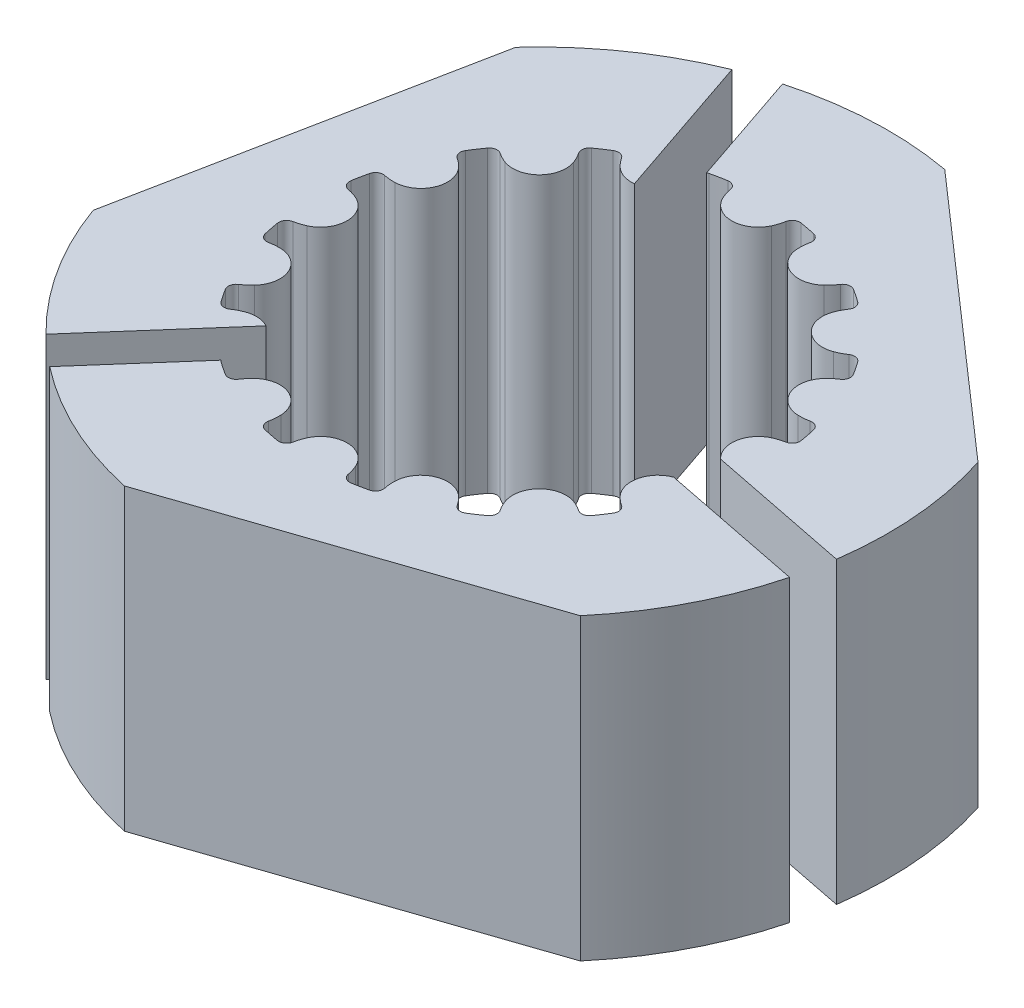
SolidWorks part; units mm, degrees
material "Alum Plate"
ref_plane "Front Plane" through (0, 0, 0) normal (0, 0, 1) x (1, 0, 0)
ref_plane "Top Plane" through (0, 0, 0) normal (0, 1, 0) x (1, 0, 0)
ref_plane "Right Plane" through (0, 0, 0) normal (1, 0, 0) x (0, 0, -1)
other "Bounding Box"
ref_plane "Default Plane" through (-8.9266, -12.7485, 0) normal (-0.1736, 0.9848, 0) x (0.9848, 0.1736, 0)
sketch "Sketch1" plane through (0, 0, 0) normal (0, 1, 0) x (1, 0, 0)
  line L0 (0, -7.8245) -> (0, 0) construction
  circle A0 centre (0, 0) radius 2.5
  arc B0 (-1.8508, -6.777) -> (-1.6633, -7.0715) centre (-1.6061, -6.8282) ccw
  arc B1 (-1.6633, -7.0715) -> (-1.1695, -7.1697) centre (0, 0) ccw
  arc B2 (-1.1695, -7.1697) -> (-0.8836, -6.9694) centre (-1.1292, -6.923) ccw
  arc B3 (-0.7739, -6.6229) -> (-0.8836, -6.9694) centre (0.61, -7.2516) ccw
  arc B4 (0.7739, -6.6229) -> (-0.7739, -6.6229) centre (0, -6.9745) ccw
  arc B5 (0.8836, -6.9694) -> (0.7739, -6.6229) centre (-0.61, -7.2516) ccw
  arc B6 (0.8836, -6.9694) -> (1.1695, -7.1697) centre (1.1292, -6.923) ccw
  arc B7 (1.1695, -7.1697) -> (1.6633, -7.0715) centre (0, 0) ccw
  arc B8 (1.6633, -7.0715) -> (1.8508, -6.777) centre (1.6061, -6.8282) ccw
  arc B9 (1.8195, -6.4149) -> (1.8508, -6.777) centre (3.3386, -6.4662) ccw
  arc B10 (3.2495, -5.8226) -> (1.8195, -6.4149) centre (2.669, -6.4436) ccw
  arc B11 (3.4834, -6.1008) -> (3.2495, -5.8226) centre (2.2115, -6.9331) ccw
  arc B12 (3.4834, -6.1008) -> (3.8242, -6.1764) centre (3.6926, -5.9639) ccw
  arc B13 (3.8242, -6.1764) -> (4.2428, -5.8967) centre (0, 0) ccw
  arc B14 (4.2428, -5.8967) -> (4.3033, -5.5529) centre (4.0968, -5.6938) ccw
  arc B15 (4.1359, -5.2303) -> (4.3033, -5.5529) centre (5.559, -4.6963) ccw
  arc B16 (5.2303, -4.1359) -> (4.1359, -5.2303) centre (4.9317, -4.9317) ccw
  arc B17 (5.5529, -4.3033) -> (5.2303, -4.1359) centre (4.6963, -5.559) ccw
  arc B18 (5.5529, -4.3033) -> (5.8967, -4.2428) centre (5.6938, -4.0968) ccw
  arc B19 (5.8967, -4.2428) -> (6.1764, -3.8242) centre (0, 0) ccw
  arc B20 (6.1764, -3.8242) -> (6.1008, -3.4834) centre (5.9639, -3.6926) ccw
  arc B21 (5.8226, -3.2495) -> (6.1008, -3.4834) centre (6.9331, -2.2115) ccw
  arc B22 (6.4149, -1.8195) -> (5.8226, -3.2495) centre (6.4436, -2.669) ccw
  arc B23 (6.777, -1.8508) -> (6.4149, -1.8195) centre (6.4662, -3.3386) ccw
  arc B24 (6.777, -1.8508) -> (7.0715, -1.6633) centre (6.8282, -1.6061) ccw
  arc B25 (7.0715, -1.6633) -> (7.1697, -1.1695) centre (0, 0) ccw
  arc B26 (7.1697, -1.1695) -> (6.9694, -0.8836) centre (6.923, -1.1292) ccw
  arc B27 (6.6229, -0.7739) -> (6.9694, -0.8836) centre (7.2516, 0.61) ccw
  arc B28 (6.6229, 0.7739) -> (6.6229, -0.7739) centre (6.9745, 0) ccw
  arc B29 (6.9694, 0.8836) -> (6.6229, 0.7739) centre (7.2516, -0.61) ccw
  arc B30 (6.9694, 0.8836) -> (7.1697, 1.1695) centre (6.923, 1.1292) ccw
  arc B31 (7.1697, 1.1695) -> (7.0715, 1.6633) centre (0, 0) ccw
  arc B32 (7.0715, 1.6633) -> (6.777, 1.8508) centre (6.8282, 1.6061) ccw
  arc B33 (6.4149, 1.8195) -> (6.777, 1.8508) centre (6.4662, 3.3386) ccw
  arc B34 (5.8226, 3.2495) -> (6.4149, 1.8195) centre (6.4436, 2.669) ccw
  arc B35 (6.1008, 3.4834) -> (5.8226, 3.2495) centre (6.9331, 2.2115) ccw
  arc B36 (6.1008, 3.4834) -> (6.1764, 3.8242) centre (5.9639, 3.6926) ccw
  arc B37 (6.1764, 3.8242) -> (5.8967, 4.2428) centre (0, 0) ccw
  arc B38 (5.8967, 4.2428) -> (5.5529, 4.3033) centre (5.6938, 4.0968) ccw
  arc B39 (5.2303, 4.1359) -> (5.5529, 4.3033) centre (4.6963, 5.559) ccw
  arc B40 (4.1359, 5.2303) -> (5.2303, 4.1359) centre (4.9317, 4.9317) ccw
  arc B41 (4.3033, 5.5529) -> (4.1359, 5.2303) centre (5.559, 4.6963) ccw
  arc B42 (4.3033, 5.5529) -> (4.2428, 5.8967) centre (4.0968, 5.6938) ccw
  arc B43 (4.2428, 5.8967) -> (3.8242, 6.1764) centre (0, 0) ccw
  arc B44 (3.8242, 6.1764) -> (3.4834, 6.1008) centre (3.6926, 5.9639) ccw
  arc B45 (3.2495, 5.8226) -> (3.4834, 6.1008) centre (2.2115, 6.9331) ccw
  arc B46 (1.8195, 6.4149) -> (3.2495, 5.8226) centre (2.669, 6.4436) ccw
  arc B47 (1.8508, 6.777) -> (1.8195, 6.4149) centre (3.3386, 6.4662) ccw
  arc B48 (1.8508, 6.777) -> (1.6633, 7.0715) centre (1.6061, 6.8282) ccw
  arc B49 (1.6633, 7.0715) -> (1.1695, 7.1697) centre (0, 0) ccw
  arc B50 (1.1695, 7.1697) -> (0.8836, 6.9694) centre (1.1292, 6.923) ccw
  arc B51 (0.7739, 6.6229) -> (0.8836, 6.9694) centre (-0.61, 7.2516) ccw
  arc B52 (-0.7739, 6.6229) -> (0.7739, 6.6229) centre (0, 6.9745) ccw
  arc B53 (-0.8836, 6.9694) -> (-0.7739, 6.6229) centre (0.61, 7.2516) ccw
  arc B54 (-0.8836, 6.9694) -> (-1.1695, 7.1697) centre (-1.1292, 6.923) ccw
  arc B55 (-1.1695, 7.1697) -> (-1.6633, 7.0715) centre (0, 0) ccw
  arc B56 (-1.6633, 7.0715) -> (-1.8508, 6.777) centre (-1.6061, 6.8282) ccw
  arc B57 (-1.8195, 6.4149) -> (-1.8508, 6.777) centre (-3.3386, 6.4662) ccw
  arc B58 (-3.2495, 5.8226) -> (-1.8195, 6.4149) centre (-2.669, 6.4436) ccw
  arc B59 (-3.4834, 6.1008) -> (-3.2495, 5.8226) centre (-2.2115, 6.9331) ccw
  arc B60 (-3.4834, 6.1008) -> (-3.8242, 6.1764) centre (-3.6926, 5.9639) ccw
  arc B61 (-3.8242, 6.1764) -> (-4.2428, 5.8967) centre (0, 0) ccw
  arc B62 (-4.2428, 5.8967) -> (-4.3033, 5.5529) centre (-4.0968, 5.6938) ccw
  arc B63 (-4.1359, 5.2303) -> (-4.3033, 5.5529) centre (-5.559, 4.6963) ccw
  arc B64 (-5.2303, 4.1359) -> (-4.1359, 5.2303) centre (-4.9317, 4.9317) ccw
  arc B65 (-5.5529, 4.3033) -> (-5.2303, 4.1359) centre (-4.6963, 5.559) ccw
  arc B66 (-5.5529, 4.3033) -> (-5.8967, 4.2428) centre (-5.6938, 4.0968) ccw
  arc B67 (-5.8967, 4.2428) -> (-6.1764, 3.8242) centre (0, 0) ccw
  arc B68 (-6.1764, 3.8242) -> (-6.1008, 3.4834) centre (-5.9639, 3.6926) ccw
  arc B69 (-5.8226, 3.2495) -> (-6.1008, 3.4834) centre (-6.9331, 2.2115) ccw
  arc B70 (-6.4149, 1.8195) -> (-5.8226, 3.2495) centre (-6.4436, 2.669) ccw
  arc B71 (-6.777, 1.8508) -> (-6.4149, 1.8195) centre (-6.4662, 3.3386) ccw
  arc B72 (-6.777, 1.8508) -> (-7.0715, 1.6633) centre (-6.8282, 1.6061) ccw
  arc B73 (-7.0715, 1.6633) -> (-7.1697, 1.1695) centre (0, 0) ccw
  arc B74 (-7.1697, 1.1695) -> (-6.9694, 0.8836) centre (-6.923, 1.1292) ccw
  arc B75 (-6.6229, 0.7739) -> (-6.9694, 0.8836) centre (-7.2516, -0.61) ccw
  arc B76 (-6.6229, -0.7739) -> (-6.6229, 0.7739) centre (-6.9745, 0) ccw
  arc B77 (-6.9694, -0.8836) -> (-6.6229, -0.7739) centre (-7.2516, 0.61) ccw
  arc B78 (-6.9694, -0.8836) -> (-7.1697, -1.1695) centre (-6.923, -1.1292) ccw
  arc B79 (-7.1697, -1.1695) -> (-7.0715, -1.6633) centre (0, 0) ccw
  arc B80 (-7.0715, -1.6633) -> (-6.777, -1.8508) centre (-6.8282, -1.6061) ccw
  arc B81 (-6.4149, -1.8195) -> (-6.777, -1.8508) centre (-6.4662, -3.3386) ccw
  arc B82 (-5.8226, -3.2495) -> (-6.4149, -1.8195) centre (-6.4436, -2.669) ccw
  arc B83 (-6.1008, -3.4834) -> (-5.8226, -3.2495) centre (-6.9331, -2.2115) ccw
  arc B84 (-6.1008, -3.4834) -> (-6.1764, -3.8242) centre (-5.9639, -3.6926) ccw
  arc B85 (-6.1764, -3.8242) -> (-5.8967, -4.2428) centre (0, 0) ccw
  arc B86 (-5.8967, -4.2428) -> (-5.5529, -4.3033) centre (-5.6938, -4.0968) ccw
  arc B87 (-5.2303, -4.1359) -> (-5.5529, -4.3033) centre (-4.6963, -5.559) ccw
  arc B88 (-4.1359, -5.2303) -> (-5.2303, -4.1359) centre (-4.9317, -4.9317) ccw
  arc B89 (-4.3033, -5.5529) -> (-4.1359, -5.2303) centre (-5.559, -4.6963) ccw
  arc B90 (-4.3033, -5.5529) -> (-4.2428, -5.8967) centre (-4.0968, -5.6938) ccw
  arc B91 (-4.2428, -5.8967) -> (-3.8242, -6.1764) centre (0, 0) ccw
  arc B92 (-3.8242, -6.1764) -> (-3.4834, -6.1008) centre (-3.6926, -5.9639) ccw
  arc B93 (-3.2495, -5.8226) -> (-3.4834, -6.1008) centre (-2.2115, -6.9331) ccw
  arc B94 (-1.8195, -6.4149) -> (-3.2495, -5.8226) centre (-2.669, -6.4436) ccw
  arc B95 (-1.8508, -6.777) -> (-1.8195, -6.4149) centre (-3.3386, -6.4662) ccw
  dimension "D1" = 5
sketch_block_instance "Block-GT2 16 Tooth Profile-1"
sketch_block "Block-GT2 16 Tooth Profile"
extrude "Boss-Extrude1" add sketch "Sketch1" along normal mid plane 9.525
sketch "Sketch2" plane through (0, -4.7625, 0) normal (0, -1, 0) x (1, 0, 0)
  circle A0 centre (0, 0) radius 7.9375
  circle A1 centre (0, 0) radius 2.5 construction
  circle A2 centre (0, 0) radius 2.5
  dimension "D1" = 15.875
extrude "Boss-Extrude2" add sketch "Sketch2" along normal blind 0.762 separate body
sketch "Sketch4" plane through (0, -4.7625, 0) normal (0, -1, 0) x (1, 0, 0)
  line L0 (-4.3596, 0.8672) -> (0, 0) construction
  line L1 (0, 0) -> (4.3596, -0.8672) construction
  line L2 (-7.1249, 1.4172) -> (-4.3596, 0.8672) construction
  circle A0 centre (-4.3596, 0.8672) radius 1
  circle A1 centre (4.3596, -0.8672) radius 1
  arc A2 (-7.0715, 1.6633) -> (-7.1697, 1.1695) centre (0, 0) ccw construction
  dimension "D1" = 2
  dimension "D2" = 4.445
extrude "Cut-Extrude2" cut sketch "Sketch4" against normal through all
sketch "Sketch5" plane through (0, -4.7625, 0) normal (0, 1, 0) x (1, 0, 0)
  circle A0 centre (-4.3596, -0.8672) radius 1.25
  circle A1 centre (4.3596, 0.8672) radius 1.25
  dimension "D1" = 2.5
extrude "Cut-Extrude3" cut sketch "Sketch5" against normal through all
delete or keep bodies "Body-Delete/Keep 1" [suppressed] type delete bodies bodies 111
delete or keep bodies "Body-Delete/Keep 2" [suppressed] type delete bodies bodies 108
sketch "Sketch6" plane through (0, 4.7625, 0) normal (0, 1, 0) x (1, 0, 0)
  line L2 (0, 0) -> (-3.572, 10.5228) construction
  line L3 (-7.327, -8.3548) -> (0, 0) construction
  line L4 (0, 0) -> (10.899, -2.1679) construction
  line L5 (-3.572, 10.5228) -> (10.899, -2.1679) construction
  line L6 (10.899, -2.1679) -> (-7.327, -8.3548) construction
  line L7 (-7.327, -8.3548) -> (-3.572, 10.5228) construction
  line L8 (-3.572, 10.5228) -> (-10.899, 2.1679) construction
  line L9 (-10.899, 2.1679) -> (-7.327, -8.3548) construction
  line L10 (-7.327, -8.3548) -> (3.572, -10.5228) construction
  line L11 (3.572, -10.5228) -> (10.899, -2.1679) construction
  line L12 (10.899, -2.1679) -> (7.327, 8.3548) construction
  line L13 (7.327, 8.3548) -> (-3.572, 10.5228) construction
  line L14 (0.6013, 0.2041) -> (-2.9707, 10.7269)
  line L15 (-6.8496, -8.7735) -> (0.4774, -0.4187)
  line L16 (-0.1239, -0.6228) -> (10.7751, -2.7907)
  line L17 (-0.6013, -0.2041) -> (-4.1733, 10.3186)
  line L18 (-7.8044, -7.9361) -> (-0.4774, 0.4187)
  line L19 (0.1239, 0.6228) -> (11.0229, -1.5451)
  line L20 (-8.2253, 7.4721) -> (-10.4586, -3.7556)
  line L21 (-2.3583, -10.8594) -> (8.4818, -7.1797)
  line L22 (1.9769, 10.9352) -> (10.5837, 3.3873)
  line L23 (7.327, 8.3548) -> (6.2803, 7.1613) construction
  line L24 (3.0617, -9.0195) -> (3.572, -10.5228) construction
  line L25 (-10.899, 2.1679) -> (-9.342, 1.8582) construction
  circle A1 centre (0, 0) radius 11.1125
  arc A96 (-1.8508, -6.777) -> (-1.8195, -6.4149) centre (-3.3386, -6.4662) ccw
  arc A97 (-1.8508, -6.777) -> (-1.6633, -7.0715) centre (-1.6061, -6.8282) ccw
  arc A98 (-1.6633, -7.0715) -> (-1.1695, -7.1697) centre (0, 0) ccw
  arc A99 (-1.1695, -7.1697) -> (-0.8836, -6.9694) centre (-1.1292, -6.923) ccw
  arc A100 (-0.7739, -6.6229) -> (-0.8836, -6.9694) centre (0.61, -7.2516) ccw
  arc A101 (0.7739, -6.6229) -> (-0.7739, -6.6229) centre (0, -6.9745) ccw
  arc A102 (0.8836, -6.9694) -> (0.7739, -6.6229) centre (-0.61, -7.2516) ccw
  arc A103 (0.8836, -6.9694) -> (1.1695, -7.1697) centre (1.1292, -6.923) ccw
  arc A104 (1.1695, -7.1697) -> (1.6633, -7.0715) centre (0, 0) ccw
  arc A105 (1.6633, -7.0715) -> (1.8508, -6.777) centre (1.6061, -6.8282) ccw
  arc A106 (1.8195, -6.4149) -> (1.8508, -6.777) centre (3.3386, -6.4662) ccw
  arc A107 (3.2495, -5.8226) -> (1.8195, -6.4149) centre (2.669, -6.4436) ccw
  arc A108 (3.4834, -6.1008) -> (3.2495, -5.8226) centre (2.2115, -6.9331) ccw
  arc A109 (3.4834, -6.1008) -> (3.8242, -6.1764) centre (3.6926, -5.9639) ccw
  arc A110 (3.8242, -6.1764) -> (4.2428, -5.8967) centre (0, 0) ccw
  arc A111 (4.2428, -5.8967) -> (4.3033, -5.5529) centre (4.0968, -5.6938) ccw
  arc A112 (4.1359, -5.2303) -> (4.3033, -5.5529) centre (5.559, -4.6963) ccw
  arc A113 (5.2303, -4.1359) -> (4.1359, -5.2303) centre (4.9317, -4.9317) ccw
  arc A114 (5.5529, -4.3033) -> (5.2303, -4.1359) centre (4.6963, -5.559) ccw
  arc A115 (5.5529, -4.3033) -> (5.8967, -4.2428) centre (5.6938, -4.0968) ccw
  arc A116 (5.8967, -4.2428) -> (6.1764, -3.8242) centre (0, 0) ccw
  arc A117 (6.1764, -3.8242) -> (6.1008, -3.4834) centre (5.9639, -3.6926) ccw
  arc A118 (5.8226, -3.2495) -> (6.1008, -3.4834) centre (6.9331, -2.2115) ccw
  arc A119 (6.4149, -1.8195) -> (5.8226, -3.2495) centre (6.4436, -2.669) ccw
  arc A120 (6.777, -1.8508) -> (6.4149, -1.8195) centre (6.4662, -3.3386) ccw
  arc A121 (6.777, -1.8508) -> (7.0715, -1.6633) centre (6.8282, -1.6061) ccw
  arc A122 (7.0715, -1.6633) -> (7.1697, -1.1695) centre (0, 0) ccw
  arc A123 (7.1697, -1.1695) -> (6.9694, -0.8836) centre (6.923, -1.1292) ccw
  arc A124 (6.6229, -0.7739) -> (6.9694, -0.8836) centre (7.2516, 0.61) ccw
  arc A125 (6.6229, 0.7739) -> (6.6229, -0.7739) centre (6.9745, 0) ccw
  arc A126 (6.9694, 0.8836) -> (6.6229, 0.7739) centre (7.2516, -0.61) ccw
  arc A127 (6.9694, 0.8836) -> (7.1697, 1.1695) centre (6.923, 1.1292) ccw
  arc A128 (7.1697, 1.1695) -> (7.0715, 1.6633) centre (0, 0) ccw
  arc A129 (7.0715, 1.6633) -> (6.777, 1.8508) centre (6.8282, 1.6061) ccw
  arc A130 (6.4149, 1.8195) -> (6.777, 1.8508) centre (6.4662, 3.3386) ccw
  arc A131 (5.8226, 3.2495) -> (6.4149, 1.8195) centre (6.4436, 2.669) ccw
  arc A132 (6.1008, 3.4834) -> (5.8226, 3.2495) centre (6.9331, 2.2115) ccw
  arc A133 (6.1008, 3.4834) -> (6.1764, 3.8242) centre (5.9639, 3.6926) ccw
  arc A134 (6.1764, 3.8242) -> (5.8967, 4.2428) centre (0, 0) ccw
  arc A135 (5.8967, 4.2428) -> (5.5529, 4.3033) centre (5.6938, 4.0968) ccw
  arc A136 (5.2303, 4.1359) -> (5.5529, 4.3033) centre (4.6963, 5.559) ccw
  arc A137 (4.1359, 5.2303) -> (5.2303, 4.1359) centre (4.9317, 4.9317) ccw
  arc A138 (4.3033, 5.5529) -> (4.1359, 5.2303) centre (5.559, 4.6963) ccw
  arc A139 (4.3033, 5.5529) -> (4.2428, 5.8967) centre (4.0968, 5.6938) ccw
  arc A140 (4.2428, 5.8967) -> (3.8242, 6.1764) centre (0, 0) ccw
  arc A141 (3.8242, 6.1764) -> (3.4834, 6.1008) centre (3.6926, 5.9639) ccw
  arc A142 (3.2495, 5.8226) -> (3.4834, 6.1008) centre (2.2115, 6.9331) ccw
  arc A143 (1.8195, 6.4149) -> (3.2495, 5.8226) centre (2.669, 6.4436) ccw
  arc A144 (1.8508, 6.777) -> (1.8195, 6.4149) centre (3.3386, 6.4662) ccw
  arc A145 (1.8508, 6.777) -> (1.6633, 7.0715) centre (1.6061, 6.8282) ccw
  arc A146 (1.6633, 7.0715) -> (1.1695, 7.1697) centre (0, 0) ccw
  arc A147 (1.1695, 7.1697) -> (0.8836, 6.9694) centre (1.1292, 6.923) ccw
  arc A148 (0.7739, 6.6229) -> (0.8836, 6.9694) centre (-0.61, 7.2516) ccw
  arc A149 (-0.7739, 6.6229) -> (0.7739, 6.6229) centre (0, 6.9745) ccw
  arc A150 (-0.8836, 6.9694) -> (-0.7739, 6.6229) centre (0.61, 7.2516) ccw
  arc A151 (-0.8836, 6.9694) -> (-1.1695, 7.1697) centre (-1.1292, 6.923) ccw
  arc A152 (-1.1695, 7.1697) -> (-1.6633, 7.0715) centre (0, 0) ccw
  arc A153 (-1.6633, 7.0715) -> (-1.8508, 6.777) centre (-1.6061, 6.8282) ccw
  arc A154 (-1.8195, 6.4149) -> (-1.8508, 6.777) centre (-3.3386, 6.4662) ccw
  arc A155 (-3.2495, 5.8226) -> (-1.8195, 6.4149) centre (-2.669, 6.4436) ccw
  arc A156 (-3.4834, 6.1008) -> (-3.2495, 5.8226) centre (-2.2115, 6.9331) ccw
  arc A157 (-3.4834, 6.1008) -> (-3.8242, 6.1764) centre (-3.6926, 5.9639) ccw
  arc A158 (-3.8242, 6.1764) -> (-4.2428, 5.8967) centre (0, 0) ccw
  arc A159 (-4.2428, 5.8967) -> (-4.3033, 5.5529) centre (-4.0968, 5.6938) ccw
  arc A160 (-4.1359, 5.2303) -> (-4.3033, 5.5529) centre (-5.559, 4.6963) ccw
  arc A161 (-5.2303, 4.1359) -> (-4.1359, 5.2303) centre (-4.9317, 4.9317) ccw
  arc A162 (-5.5529, 4.3033) -> (-5.2303, 4.1359) centre (-4.6963, 5.559) ccw
  arc A163 (-5.5529, 4.3033) -> (-5.8967, 4.2428) centre (-5.6938, 4.0968) ccw
  arc A164 (-5.8967, 4.2428) -> (-6.1764, 3.8242) centre (0, 0) ccw
  arc A165 (-6.1764, 3.8242) -> (-6.1008, 3.4834) centre (-5.9639, 3.6926) ccw
  arc A166 (-5.8226, 3.2495) -> (-6.1008, 3.4834) centre (-6.9331, 2.2115) ccw
  arc A167 (-6.4149, 1.8195) -> (-5.8226, 3.2495) centre (-6.4436, 2.669) ccw
  arc A168 (-6.777, 1.8508) -> (-6.4149, 1.8195) centre (-6.4662, 3.3386) ccw
  arc A169 (-6.777, 1.8508) -> (-7.0715, 1.6633) centre (-6.8282, 1.6061) ccw
  arc A170 (-7.0715, 1.6633) -> (-7.1697, 1.1695) centre (0, 0) ccw
  arc A171 (-7.1697, 1.1695) -> (-6.9694, 0.8836) centre (-6.923, 1.1292) ccw
  arc A172 (-6.6229, 0.7739) -> (-6.9694, 0.8836) centre (-7.2516, -0.61) ccw
  arc A173 (-6.6229, -0.7739) -> (-6.6229, 0.7739) centre (-6.9745, 0) ccw
  arc A174 (-6.9694, -0.8836) -> (-6.6229, -0.7739) centre (-7.2516, 0.61) ccw
  arc A175 (-6.9694, -0.8836) -> (-7.1697, -1.1695) centre (-6.923, -1.1292) ccw
  arc A176 (-7.1697, -1.1695) -> (-7.0715, -1.6633) centre (0, 0) ccw
  arc A177 (-7.0715, -1.6633) -> (-6.777, -1.8508) centre (-6.8282, -1.6061) ccw
  arc A178 (-6.4149, -1.8195) -> (-6.777, -1.8508) centre (-6.4662, -3.3386) ccw
  arc A179 (-5.8226, -3.2495) -> (-6.4149, -1.8195) centre (-6.4436, -2.669) ccw
  arc A180 (-6.1008, -3.4834) -> (-5.8226, -3.2495) centre (-6.9331, -2.2115) ccw
  arc A181 (-6.1008, -3.4834) -> (-6.1764, -3.8242) centre (-5.9639, -3.6926) ccw
  arc A182 (-6.1764, -3.8242) -> (-5.8967, -4.2428) centre (0, 0) ccw
  arc A183 (-5.8967, -4.2428) -> (-5.5529, -4.3033) centre (-5.6938, -4.0968) ccw
  arc A184 (-5.2303, -4.1359) -> (-5.5529, -4.3033) centre (-4.6963, -5.559) ccw
  arc A185 (-4.1359, -5.2303) -> (-5.2303, -4.1359) centre (-4.9317, -4.9317) ccw
  arc A186 (-4.3033, -5.5529) -> (-4.1359, -5.2303) centre (-5.559, -4.6963) ccw
  arc A187 (-4.3033, -5.5529) -> (-4.2428, -5.8967) centre (-4.0968, -5.6938) ccw
  arc A188 (-4.2428, -5.8967) -> (-3.8242, -6.1764) centre (0, 0) ccw
  arc A189 (-3.8242, -6.1764) -> (-3.4834, -6.1008) centre (-3.6926, -5.9639) ccw
  arc A190 (-3.2495, -5.8226) -> (-3.4834, -6.1008) centre (-2.2115, -6.9331) ccw
  arc A191 (-1.8195, -6.4149) -> (-3.2495, -5.8226) centre (-2.669, -6.4436) ccw
  arc A192 (-1.8508, -6.777) -> (-1.8195, -6.4149) centre (-3.3386, -6.4662) ccw
  arc A193 (-1.8508, -6.777) -> (-1.6633, -7.0715) centre (-1.6061, -6.8282) ccw
  arc A194 (-1.6633, -7.0715) -> (-1.1695, -7.1697) centre (0, 0) ccw
  arc A195 (-1.1695, -7.1697) -> (-0.8836, -6.9694) centre (-1.1292, -6.923) ccw
  arc A196 (-0.7739, -6.6229) -> (-0.8836, -6.9694) centre (0.61, -7.2516) ccw
  arc A197 (0.7739, -6.6229) -> (-0.7739, -6.6229) centre (0, -6.9745) ccw
  arc A198 (0.8836, -6.9694) -> (0.7739, -6.6229) centre (-0.61, -7.2516) ccw
  arc A199 (0.8836, -6.9694) -> (1.1695, -7.1697) centre (1.1292, -6.923) ccw
  arc A200 (1.1695, -7.1697) -> (1.6633, -7.0715) centre (0, 0) ccw
  arc A201 (1.6633, -7.0715) -> (1.8508, -6.777) centre (1.6061, -6.8282) ccw
  arc A202 (1.8195, -6.4149) -> (1.8508, -6.777) centre (3.3386, -6.4662) ccw
  arc A203 (3.2495, -5.8226) -> (1.8195, -6.4149) centre (2.669, -6.4436) ccw
  arc A204 (3.4834, -6.1008) -> (3.2495, -5.8226) centre (2.2115, -6.9331) ccw
  arc A205 (3.4834, -6.1008) -> (3.8242, -6.1764) centre (3.6926, -5.9639) ccw
  arc A206 (3.8242, -6.1764) -> (4.2428, -5.8967) centre (0, 0) ccw
  arc A207 (4.2428, -5.8967) -> (4.3033, -5.5529) centre (4.0968, -5.6938) ccw
  arc A208 (4.1359, -5.2303) -> (4.3033, -5.5529) centre (5.559, -4.6963) ccw
  arc A209 (5.2303, -4.1359) -> (4.1359, -5.2303) centre (4.9317, -4.9317) ccw
  arc A210 (5.5529, -4.3033) -> (5.2303, -4.1359) centre (4.6963, -5.559) ccw
  arc A211 (5.5529, -4.3033) -> (5.8967, -4.2428) centre (5.6938, -4.0968) ccw
  arc A212 (5.8967, -4.2428) -> (6.1764, -3.8242) centre (0, 0) ccw
  arc A213 (6.1764, -3.8242) -> (6.1008, -3.4834) centre (5.9639, -3.6926) ccw
  arc A214 (5.8226, -3.2495) -> (6.1008, -3.4834) centre (6.9331, -2.2115) ccw
  arc A215 (6.4149, -1.8195) -> (5.8226, -3.2495) centre (6.4436, -2.669) ccw
  arc A216 (6.777, -1.8508) -> (6.4149, -1.8195) centre (6.4662, -3.3386) ccw
  arc A217 (6.777, -1.8508) -> (7.0715, -1.6633) centre (6.8282, -1.6061) ccw
  arc A218 (7.0715, -1.6633) -> (7.1697, -1.1695) centre (0, 0) ccw
  arc A219 (7.1697, -1.1695) -> (6.9694, -0.8836) centre (6.923, -1.1292) ccw
  arc A220 (6.6229, -0.7739) -> (6.9694, -0.8836) centre (7.2516, 0.61) ccw
  arc A221 (6.6229, 0.7739) -> (6.6229, -0.7739) centre (6.9745, 0) ccw
  arc A222 (6.9694, 0.8836) -> (6.6229, 0.7739) centre (7.2516, -0.61) ccw
  arc A223 (6.9694, 0.8836) -> (7.1697, 1.1695) centre (6.923, 1.1292) ccw
  arc A224 (7.1697, 1.1695) -> (7.0715, 1.6633) centre (0, 0) ccw
  arc A225 (7.0715, 1.6633) -> (6.777, 1.8508) centre (6.8282, 1.6061) ccw
  arc A226 (6.4149, 1.8195) -> (6.777, 1.8508) centre (6.4662, 3.3386) ccw
  arc A227 (5.8226, 3.2495) -> (6.4149, 1.8195) centre (6.4436, 2.669) ccw
  arc A228 (6.1008, 3.4834) -> (5.8226, 3.2495) centre (6.9331, 2.2115) ccw
  arc A229 (6.1008, 3.4834) -> (6.1764, 3.8242) centre (5.9639, 3.6926) ccw
  arc A230 (6.1764, 3.8242) -> (5.8967, 4.2428) centre (0, 0) ccw
  arc A231 (5.8967, 4.2428) -> (5.5529, 4.3033) centre (5.6938, 4.0968) ccw
  arc A232 (5.2303, 4.1359) -> (5.5529, 4.3033) centre (4.6963, 5.559) ccw
  arc A233 (4.1359, 5.2303) -> (5.2303, 4.1359) centre (4.9317, 4.9317) ccw
  arc A234 (4.3033, 5.5529) -> (4.1359, 5.2303) centre (5.559, 4.6963) ccw
  arc A235 (4.3033, 5.5529) -> (4.2428, 5.8967) centre (4.0968, 5.6938) ccw
  arc A236 (4.2428, 5.8967) -> (3.8242, 6.1764) centre (0, 0) ccw
  arc A237 (3.8242, 6.1764) -> (3.4834, 6.1008) centre (3.6926, 5.9639) ccw
  arc A238 (3.2495, 5.8226) -> (3.4834, 6.1008) centre (2.2115, 6.9331) ccw
  arc A239 (1.8195, 6.4149) -> (3.2495, 5.8226) centre (2.669, 6.4436) ccw
  arc A240 (1.8508, 6.777) -> (1.8195, 6.4149) centre (3.3386, 6.4662) ccw
  arc A241 (1.8508, 6.777) -> (1.6633, 7.0715) centre (1.6061, 6.8282) ccw
  arc A242 (1.6633, 7.0715) -> (1.1695, 7.1697) centre (0, 0) ccw
  arc A243 (1.1695, 7.1697) -> (0.8836, 6.9694) centre (1.1292, 6.923) ccw
  arc A244 (0.7739, 6.6229) -> (0.8836, 6.9694) centre (-0.61, 7.2516) ccw
  arc A245 (-0.7739, 6.6229) -> (0.7739, 6.6229) centre (0, 6.9745) ccw
  arc A246 (-0.8836, 6.9694) -> (-0.7739, 6.6229) centre (0.61, 7.2516) ccw
  arc A247 (-0.8836, 6.9694) -> (-1.1695, 7.1697) centre (-1.1292, 6.923) ccw
  arc A248 (-1.1695, 7.1697) -> (-1.6633, 7.0715) centre (0, 0) ccw
  arc A249 (-1.6633, 7.0715) -> (-1.8508, 6.777) centre (-1.6061, 6.8282) ccw
  arc A250 (-1.8195, 6.4149) -> (-1.8508, 6.777) centre (-3.3386, 6.4662) ccw
  arc A251 (-3.2495, 5.8226) -> (-1.8195, 6.4149) centre (-2.669, 6.4436) ccw
  arc A252 (-3.4834, 6.1008) -> (-3.2495, 5.8226) centre (-2.2115, 6.9331) ccw
  arc A253 (-3.4834, 6.1008) -> (-3.8242, 6.1764) centre (-3.6926, 5.9639) ccw
  arc A254 (-3.8242, 6.1764) -> (-4.2428, 5.8967) centre (0, 0) ccw
  arc A255 (-4.2428, 5.8967) -> (-4.3033, 5.5529) centre (-4.0968, 5.6938) ccw
  arc A256 (-4.1359, 5.2303) -> (-4.3033, 5.5529) centre (-5.559, 4.6963) ccw
  arc A257 (-5.2303, 4.1359) -> (-4.1359, 5.2303) centre (-4.9317, 4.9317) ccw
  arc A258 (-5.5529, 4.3033) -> (-5.2303, 4.1359) centre (-4.6963, 5.559) ccw
  arc A259 (-5.5529, 4.3033) -> (-5.8967, 4.2428) centre (-5.6938, 4.0968) ccw
  arc A260 (-5.8967, 4.2428) -> (-6.1764, 3.8242) centre (0, 0) ccw
  arc A261 (-6.1764, 3.8242) -> (-6.1008, 3.4834) centre (-5.9639, 3.6926) ccw
  arc A262 (-5.8226, 3.2495) -> (-6.1008, 3.4834) centre (-6.9331, 2.2115) ccw
  arc A263 (-6.4149, 1.8195) -> (-5.8226, 3.2495) centre (-6.4436, 2.669) ccw
  arc A264 (-6.777, 1.8508) -> (-6.4149, 1.8195) centre (-6.4662, 3.3386) ccw
  arc A265 (-6.777, 1.8508) -> (-7.0715, 1.6633) centre (-6.8282, 1.6061) ccw
  arc A266 (-7.0715, 1.6633) -> (-7.1697, 1.1695) centre (0, 0) ccw
  arc A267 (-7.1697, 1.1695) -> (-6.9694, 0.8836) centre (-6.923, 1.1292) ccw
  arc A268 (-6.6229, 0.7739) -> (-6.9694, 0.8836) centre (-7.2516, -0.61) ccw
  arc A269 (-6.6229, -0.7739) -> (-6.6229, 0.7739) centre (-6.9745, 0) ccw
  arc A270 (-6.9694, -0.8836) -> (-6.6229, -0.7739) centre (-7.2516, 0.61) ccw
  arc A271 (-6.9694, -0.8836) -> (-7.1697, -1.1695) centre (-6.923, -1.1292) ccw
  arc A272 (-7.1697, -1.1695) -> (-7.0715, -1.6633) centre (0, 0) ccw
  arc A273 (-7.0715, -1.6633) -> (-6.777, -1.8508) centre (-6.8282, -1.6061) ccw
  arc A274 (-6.4149, -1.8195) -> (-6.777, -1.8508) centre (-6.4662, -3.3386) ccw
  arc A275 (-5.8226, -3.2495) -> (-6.4149, -1.8195) centre (-6.4436, -2.669) ccw
  arc A276 (-6.1008, -3.4834) -> (-5.8226, -3.2495) centre (-6.9331, -2.2115) ccw
  arc A277 (-6.1008, -3.4834) -> (-6.1764, -3.8242) centre (-5.9639, -3.6926) ccw
  arc A278 (-6.1764, -3.8242) -> (-5.8967, -4.2428) centre (0, 0) ccw
  arc A279 (-5.8967, -4.2428) -> (-5.5529, -4.3033) centre (-5.6938, -4.0968) ccw
  arc A280 (-5.2303, -4.1359) -> (-5.5529, -4.3033) centre (-4.6963, -5.559) ccw
  arc A281 (-4.1359, -5.2303) -> (-5.2303, -4.1359) centre (-4.9317, -4.9317) ccw
  arc A282 (-4.3033, -5.5529) -> (-4.1359, -5.2303) centre (-5.559, -4.6963) ccw
  arc A283 (-4.3033, -5.5529) -> (-4.2428, -5.8967) centre (-4.0968, -5.6938) ccw
  arc A284 (-4.2428, -5.8967) -> (-3.8242, -6.1764) centre (0, 0) ccw
  arc A285 (-3.8242, -6.1764) -> (-3.4834, -6.1008) centre (-3.6926, -5.9639) ccw
  arc A286 (-3.2495, -5.8226) -> (-3.4834, -6.1008) centre (-2.2115, -6.9331) ccw
  arc A287 (-1.8195, -6.4149) -> (-3.2495, -5.8226) centre (-2.669, -6.4436) ccw
  point P99 (7.1249, -1.4172)
  dimension "D2" = 0.635
  dimension "D4" = 0.635
  dimension "D3" = 22.225
  dimension "D5" = 9.525
  dimension "D1" = 0
extrude "Boss-Extrude3" add sketch "Sketch6" against normal up to surface (9.525 mm away) separate body contours A192 A287 L17 A1 L20 L18 A221 A220 A219 A218 A217 A216 A215 A214 A213 A212 A211 A210 A209 A208 A207 A206 A205 A204 A203 A202 A201 A200 A199 A198 A197 A196 A195 A194 A193 | A284 A283 A282 A281 A280 A279 A278 A277 A276 A275 A274 A273 A272 A271 A270 A269 A268 A267 A266 A265 A264 A263 A262 A261 A260 A259 A258 A257 A256 A255 A254 L19 A1 L22 L14 | L16 A251 A250 A249 A248 A247 A246 A245 A244 A243 A242 A241 A240 A239 A238 A237 A236 A235 A234 A233 A232 A231 A230 A229 A228 A227 A226 A225 A224 A223 A222 A221 L15 A1 L21 region at (4.7876, 4.7625, -5.4005) region at (-3.5574, 4.7625, -7.8865) region at (2.3565, 4.7625, 6.8216) up to face at (-4.3596, -4.7625, 2.1172)
delete or keep bodies "Body-Delete/Keep 3" type delete bodies bodies 108 111
